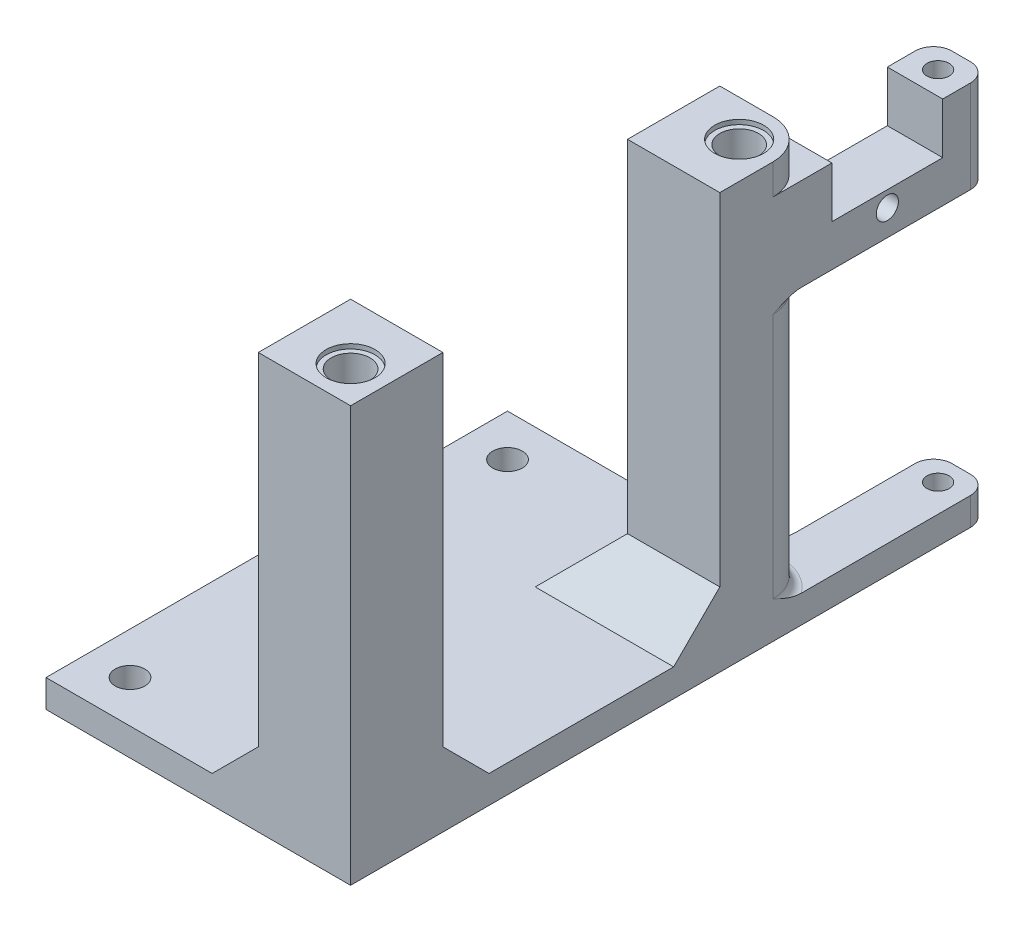
SolidWorks part; units mm, degrees
ref_plane "Front Plane" through (0, 0, 0) normal (0, 0, 1) x (1, 0, 0)
ref_plane "Top Plane" through (0, 0, 0) normal (0, 1, 0) x (1, 0, 0)
ref_plane "Right Plane" through (0, 0, 0) normal (1, 0, 0) x (0, 0, -1)
sketch "Sketch1" plane through (0, 0, 0) normal (0, 1, 0) x (1, 0, 0)
  line L1 (-6.5124, 9.686) -> (1.4876, 9.686)
  line L2 (-6.5124, 9.686) -> (-6.5124, -40.314)
  line L3 (-6.5124, -40.314) -> (1.4876, -40.314)
  line L4 (1.4876, 9.686) -> (1.4876, -40.314)
  line L5 (1.4876, 9.686) -> (26.4876, 9.686)
  line L6 (1.4876, 9.686) -> (1.4876, -40.314)
  line L7 (1.4876, -40.314) -> (26.4876, -40.314)
  line L8 (26.4876, 9.686) -> (26.4876, -40.314)
  circle A0 centre (-1.9624, -35.764) radius 1.6
  circle A1 centre (-1.9624, 5.136) radius 1.6
  dimension "D4" = 3.2
  dimension "D5" = 3.2
  dimension "D6" = 4.55
  dimension "D7" = 4.55
  dimension "D8" = 4.55
  dimension "D9" = 4.55
  dimension "D1" = 8
  dimension "D2" = 50
  dimension "D3" = 25
extrude "Boss-Extrude1" add sketch "Sketch1" along normal blind 3 contours A1 | A0 | L5 L8 L7 L3 L2 L1
sketch "Sketch2" plane through (0, 3, 0) normal (0, 1, 0) x (1, 0, 0)
  line L1 (26.4876, -40.314) -> (16.4876, -40.314)
  line L2 (26.4876, -40.314) -> (26.4876, -30.314)
  line L3 (26.4876, -30.314) -> (16.4876, -30.314)
  line L4 (16.4876, -40.314) -> (16.4876, -30.314)
  line L5 (26.4876, 9.686) -> (16.4876, 9.686)
  line L6 (26.4876, 9.686) -> (26.4876, -0.314)
  line L7 (26.4876, -0.314) -> (16.4876, -0.314)
  line L8 (16.4876, 9.686) -> (16.4876, -0.314)
  dimension "D1" = 10
  dimension "D2" = 10
  dimension "D3" = 10
  dimension "D4" = 10
extrude "Boss-Extrude2" add sketch "Sketch2" along normal blind 42
chamfer "Chamfer1" distance 5 angle 45 4 edges at (16.4876, 3, -4.686) (21.4876, 3, 0.314) (16.4876, 3, 35.314) (21.4876, 3, 30.314)
ref_plane "Plane1" through (0, 45, 0) normal (0, 1, 0) x (1, 0, 0)
sketch "Sketch3" plane through (0, 45, 0) normal (0, 1, 0) x (1, 0, 0)
  line L0 (26.4876, -40.314) -> (26.4876, -30.314) construction
  line L1 (16.4876, -40.314) -> (26.4876, -40.314) construction
  line L2 (26.4876, -0.314) -> (26.4876, 9.686) construction
  line L3 (26.4876, 9.686) -> (16.4876, 9.686) construction
  circle A0 centre (22.5376, -36.364) radius 2.1
  circle A1 centre (22.5376, 5.736) radius 2.1
  dimension "D1" = 4.2
  dimension "D3" = 3.95
  dimension "D4" = 4.2
  dimension "D6" = 3.95
  dimension "D2" = 3.95
  dimension "D5" = 3.95
extrude "Cut-Extrude1" cut sketch "Sketch3" against normal blind 52
sketch "Sketch4" plane through (0, 45, 0) normal (0, 1, 0) x (1, 0, 0)
  circle A0 centre (22.5376, -36.364) radius 2.65
  circle A1 centre (22.5376, 5.736) radius 2.65
  dimension "D1" = 5.3
  dimension "D2" = 5.3
extrude "Cut-Extrude2" cut sketch "Sketch4" against normal blind 0.5
ref_plane "Plane2" through (0, 22.5, 0) normal (0, -1, 0) x (-1, 0, 0)
mirror "Mirror1" about plane through (0, 22.5, 0) normal (0, -1, 0) of "Cut-Extrude2"
sketch "Sketch5" plane through (0, 0, -9.686) normal (0, 0, -1) x (-1, 0, 0)
  line L0 (-22.4876, 36.5) -> (-17.9876, 36.5) construction
  line L1 (-20.4876, 36.2) -> (-26.4876, 36.2)
  line L2 (-20.4876, 36.2) -> (-20.4876, 31.6868)
  line L3 (-20.4876, 31.6868) -> (-26.4876, 31.6868)
  line L4 (-26.4876, 36.2) -> (-26.4876, 31.6868)
  line L7 (-26.4876, 45) -> (-26.4876, 0) construction
  point P8 (0, 0)
  point P9 (-24.2876, 36.2)
  point P10 (0, 0)
  point P11 (0, 0)
  dimension "D1" = 0.3
  dimension "D3" = 6
extrude "Boss-Extrude3" add sketch "Sketch5" along normal up to surface (14.15 mm away)
sketch "Sketch6" plane through (26.4876, 0, 0) normal (1, 0, 0) x (0, 0, -1)
  circle A0 centre (17.836, 34.5) radius 1.2
  dimension "D1" = 2.4
extrude "Cut-Extrude3" cut sketch "Sketch6" against normal up to surface (6 mm away) up to face at (20.4876, 33.9434, -16.761)
sketch "Sketch7" plane through (0, 0, -23.836) normal (0, 0, -1) x (-1, 0, 0)
  line L1 (-26.4876, 31.6868) -> (-20.4876, 31.6868)
  line L2 (-26.4876, 31.6868) -> (-26.4876, 41.7057)
  line L3 (-26.4876, 41.7057) -> (-20.4876, 41.7057)
  line L4 (-20.4876, 31.6868) -> (-20.4876, 41.7057)
extrude "Boss-Extrude4" add sketch "Sketch7" along normal blind 5
sketch "Sketch8" plane through (0, 0, -9.686) normal (0, 0, -1) x (-1, 0, 0)
  line L0 (-20.4876, 41.7057) -> (-26.4876, 41.7057) construction
  line L1 (-26.4876, 36.2) -> (-18.2687, 36.2)
  line L2 (-26.4876, 36.2) -> (-26.4876, 41.7057)
  line L3 (-26.4876, 41.7057) -> (-18.2687, 41.7057)
  line L4 (-18.2687, 36.2) -> (-18.2687, 41.7057)
extrude "Boss-Extrude5" add sketch "Sketch8" along normal up to surface (2.15 mm away)
sketch "Sketch9" plane through (0, 0, -9.686) normal (0, 0, -1) x (-1, 0, 0)
  line L0 (6.5124, 0) -> (-26.4876, 0) construction
  line L1 (-26.4876, 0) -> (-20.4876, 0)
  line L2 (-26.4876, 0) -> (-26.4876, 3)
  line L3 (-26.4876, 3) -> (-20.4876, 3)
  line L4 (-20.4876, 0) -> (-20.4876, 3)
  line L5 (6.5124, 3) -> (-11.4876, 3) construction
  line L6 (-26.4876, 41.7057) -> (-26.4876, 31.6868) construction
  line L7 (-20.4876, 31.6868) -> (-20.4876, 41.7057) construction
extrude "Boss-Extrude6" add sketch "Sketch9" along normal up to surface (19.15 mm away) up to face at (23.4876, 36.6962, -28.836)
sketch "Sketch10" plane through (0, 41.7057, 0) normal (0, 1, 0) x (1, 0, 0)
  line L0 (20.4876, 23.836) -> (26.4876, 28.836) construction
  line L1 (20.4876, 28.836) -> (26.4876, 23.836) construction
  circle A0 centre (23.4876, 26.336) radius 1.2
  dimension "D1" = 2.4
extrude "Cut-Extrude4" cut sketch "Sketch10" against normal through all
fillet "Fillet3" radius 2 4 edges at (20.4876, 1.5, -28.836) (26.4876, 1.5, -28.836) (20.4876, 36.6962, -28.836) (26.4876, 36.6962, -28.836)
fillet "Fillet4" radius 4.25 1 edges at (26.4876, 17.3434, -9.686)
fillet "Fillet5" radius 4.25 1 edges at (20.4876, 1.5, -9.686)
fillet "Fillet6" radius 4.25 1 edges at (26.4876, 43.3528, -9.686)
fillet "Fillet7" radius 4.25 1 edges at (20.4876, 33.9434, -9.686)
fillet "Fillet8" radius 1 2 edges at (19.2376, 3, -9.686) (25.2428, 3, -8.4412)
fillet "Fillet9" radius 1 2 edges at (19.3626, 31.6868, -9.686) (25.2428, 31.6868, -8.4412)
sketch "Sketch11" plane through (0, 0, 40.314) normal (0, 0, 1) x (1, 0, 0)
  line L0 (16.4876, 45) -> (26.4876, 45) construction
  line L1 (18.4876, 45) -> (24.4876, 45)
  line L2 (18.4876, 45) -> (18.4876, 42)
  line L3 (18.4876, 42) -> (24.4876, 42)
  line L4 (24.4876, 45) -> (24.4876, 42)
  line L5 (-6.5124, 0) -> (26.4876, 0) construction
  line L6 (18.4876, 0) -> (24.4876, 0)
  line L7 (18.4876, 0) -> (18.4876, 3)
  line L8 (18.4876, 3) -> (24.4876, 3)
  line L9 (24.4876, 0) -> (24.4876, 3)
  line L10 (21.4876, 8) -> (21.4876, 0) construction
  line L11 (21.4876, 8) -> (21.4876, 45) construction
  line L13 (-6.5124, 3) -> (11.4876, 3) construction
  line L14 (16.4876, 8) -> (26.4876, 8) construction
  line L15 (26.4876, 8) -> (39.3241, 4.4212) construction
  line L16 (39.3241, 4.4212) -> (39.5028, 4.4212) construction
  dimension "D1" = 3
  dimension "D2" = 3
  dimension "D3" = 3
  dimension "D4" = 3
  dimension "D5" = 3
